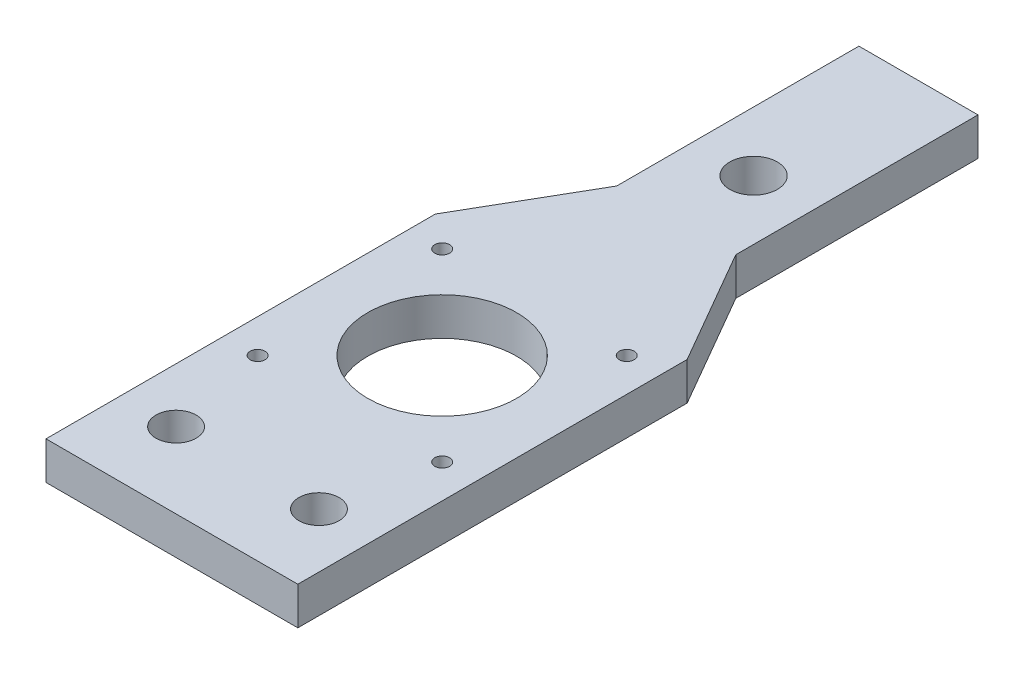
SolidWorks part; units mm, degrees
ref_plane "Front Plane" through (0, 0, 0) normal (0, 0, 1) x (1, 0, 0)
ref_plane "Top Plane" through (0, 0, 0) normal (0, 1, 0) x (1, 0, 0)
ref_plane "Right Plane" through (0, 0, 0) normal (1, 0, 0) x (0, 0, -1)
sketch "Sketch2" plane through (0, 0, 0) normal (0, 1, 0) x (1, 0, 0)
  line L0 (10, 0) -> (10, -100) construction
  line L1 (0, 0) -> (20, 0)
  line L2 (0, 0) -> (0, -100)
  line L3 (0, -100) -> (20, -100)
  line L4 (20, 0) -> (20, -100)
  line L5 (-11.15, -60) -> (0, -40.6876)
  line L6 (-11.15, -100) -> (31.15, -100)
  line L7 (-11.15, -100) -> (-11.15, -60)
  line L8 (-11.15, -60) -> (31.15, -60)
  line L9 (31.15, -100) -> (31.15, -60)
  line L10 (-11.15, -100) -> (31.15, -60) construction
  line L11 (-11.15, -60) -> (31.15, -100) construction
  line L12 (20, -40.6876) -> (31.15, -60)
  circle A0 centre (10, -80) radius 12.5
  circle A1 centre (10, -27.7) radius 4
  dimension "D3" = 8
  dimension "D4" = 25
  dimension "D1" = 100
  dimension "D2" = 20
  dimension "D5" = 52.3
  dimension "D6" = 20
  dimension "D8" = 42.3
  dimension "D9" = 60
  dimension "D10" = 60
extrude "Boss-Extrude1" add sketch "Sketch2" along normal blind 6.35 contours L2 L8 L4 L1 A1 | L5 L8 L2 | L12 L4 L8 | A0 L4 L8 L2 | A0 L2 L3 L4 | A0 L2 L8 L7 L6 | A0 L4 L6 L9 L8 region at (10, 0, 0.6325) region at (-3.7167, 0, 53.5625) region at (23.7167, 0, 53.5625) region at (10, 0, 64.6159) region at (-5.8524, 0, 80) region at (25.8524, 0, 80) region at (10, 0, 95.3841)
sketch "Sketch3" plane through (0, 6.35, 0) normal (0, 1, 0) x (1, 0, 0)
  line L1 (-5.5, -95.5) -> (25.5, -95.5) construction
  line L2 (-5.5, -95.5) -> (-5.5, -64.5) construction
  line L3 (-5.5, -64.5) -> (25.5, -64.5) construction
  line L4 (25.5, -95.5) -> (25.5, -64.5) construction
  line L5 (-5.5, -95.5) -> (25.5, -64.5) construction
  line L6 (-5.5, -64.5) -> (25.5, -95.5) construction
  point P0 (10, -80)
  dimension "D1" = 31
hole_wizard "Tap Drill for M3x0.5 Tap1" positions "Sketch4" profile "Sketch5" hole size "M3x0.5" standard "ANSI Metric" end condition through all
sketch "Sketch4" plane through (0, 6.35, 0) normal (0, 1, 0) x (1, 0, 0)
  point P0 (-5.5, -64.5)
  point P3 (25.5, -64.5)
  point P6 (25.5, -95.5)
  point P9 (-5.5, -95.5)
sketch "Sketch5" plane through (-5.5, 6.35, 64.5) normal (1, 0, 0) x (0, 0, 1)
  line L0 (0, 0) -> (0, 6.35)
  line L1 (0, 6.35) -> (1.25, 6.35)
  line L2 (1.25, 6.35) -> (1.25, 0)
  line L5 (1.25, 0) -> (0, 0)
  line L11 (0, -6.35) -> (0, 107.95) construction
  dimension "Thru Hole Dia." = 2.5
  dimension "Thru Hole Depth" = 6.35
sketch "Sketch7" plane through (0, 6.35, 0) normal (0, 1, 0) x (1, 0, 0)
  line L1 (-11.15, -100) -> (31.15, -100)
  line L2 (-11.15, -100) -> (-11.15, -125.4)
  line L3 (-11.15, -125.4) -> (31.15, -125.4)
  line L4 (31.15, -100) -> (31.15, -125.4)
  line L5 (-11.15, -100) -> (-11.15, -60) construction
  point P4 (-11.15, -101.15)
  point P5 (31.15, -100)
  point P7 (0, 0)
  dimension "D1" = 25.4
extrude "Boss-Extrude2" add sketch "Sketch7" against normal up to surface (6.35 mm away) up to face at (-5.5, 0, 65.75)
sketch "Sketch8" plane through (0, 6.35, 0) normal (0, 1, 0) x (1, 0, 0)
  line L0 (10, -125.4) -> (10, -112.7) construction
  line L1 (-11.15, -125.4) -> (31.15, -125.4) construction
  line L2 (-2, -112.7) -> (22, -112.7) construction
  point P4 (0, 0)
  point P7 (10, -112.7)
  dimension "D1" = 12.7
  dimension "D2" = 24
hole_wizard "1/4 Clearance Hole1" positions "Sketch9" profile "Sketch10" hole size "1/4" standard "ANSI Inch" end condition through all
sketch "Sketch9" plane through (0, 6.35, 0) normal (0, 1, 0) x (1, 0, 0)
  point P0 (-2, -112.7)
  point P3 (22, -112.7)
sketch "Sketch10" plane through (-2, 6.35, 112.7) normal (1, 0, 0) x (0, 0, 1)
  line L0 (0, 0) -> (0, 6.35)
  line L1 (0, 6.35) -> (3.3782, 6.35)
  line L2 (3.3782, 6.35) -> (3.3782, 0)
  line L5 (3.3782, 0) -> (0, 0)
  line L11 (0, -6.35) -> (0, 107.95) construction
  dimension "Thru Hole Dia." = 6.7564
  dimension "Thru Hole Depth" = 6.35
